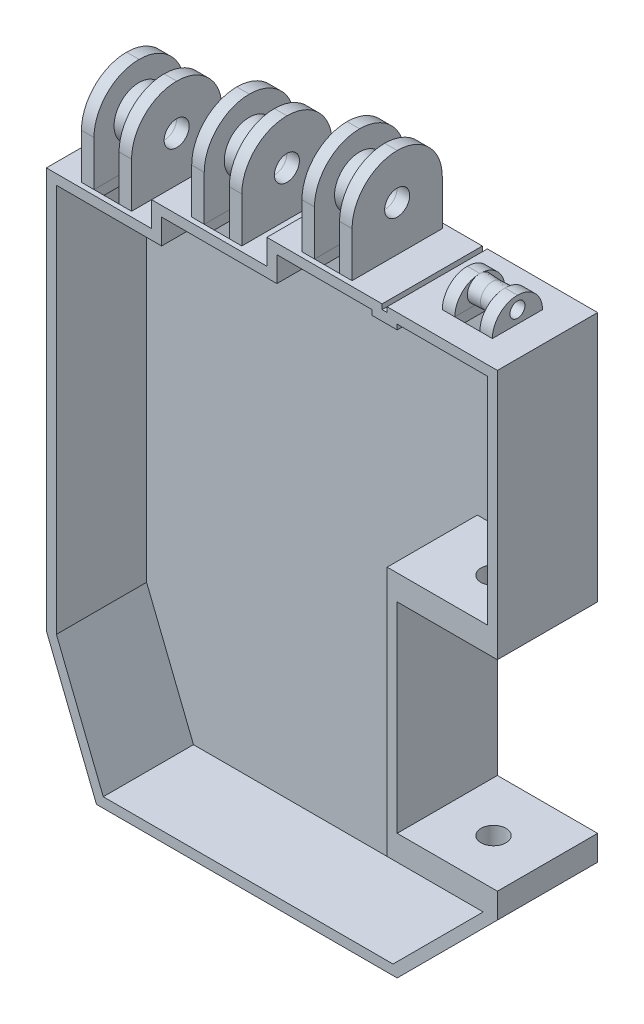
SolidWorks part; units mm, degrees
ref_plane "Front Plane" through (0, 0, 0) normal (0, 0, 1) x (1, 0, 0)
ref_plane "Top Plane" through (0, 0, 0) normal (0, 1, 0) x (1, 0, 0)
ref_plane "Right Plane" through (0, 0, 0) normal (1, 0, 0) x (0, 0, -1)
sketch "Sketch1" plane through (0, 0, 0) normal (0, 0, 1) x (1, 0, 0)
  line L0 (0, 0) -> (60, 0)
  line L1 (60, 0) -> (80, 20)
  line L2 (80, 20) -> (80, 115)
  line L3 (80, 115) -> (58, 115)
  line L4 (-10, 105) -> (11, 105)
  line L5 (-10, 105) -> (-10, 25)
  line L6 (-10, 25) -> (0, 0)
  line L7 (57, 115) -> (57, 114)
  line L8 (35, 115) -> (57, 115)
  line L9 (34, 115) -> (34, 110)
  line L10 (35, 115) -> (34, 115)
  line L11 (34, 110) -> (12, 110)
  line L12 (12, 110) -> (11, 110)
  line L13 (11, 110) -> (11, 105)
  line L14 (57, 115) -> (58, 115)
  line L15 (57, 114) -> (58, 114)
  line L16 (58, 114) -> (58, 115)
  dimension "D1" = 60
  dimension "D2" = 22
  dimension "D3" = 90
  dimension "D4" = 20
  dimension "D5" = 80
  dimension "D6" = 95
  dimension "D7" = 135
  dimension "D8" = 1
  dimension "D9" = 22
  dimension "D10" = 22
  dimension "D11" = 1
  dimension "D12" = 5
  dimension "D13" = 1
  dimension "D14" = 5
  dimension "D15" = 1
extrude "Boss-Extrude1" add sketch "Sketch1" along normal blind 20 contours L16 L15 L7 L8 L10 L9 L11 L12 L13 L4 L5 L6 L0 L1 L2 L3 region at (35.6394, 57.3872, 0)
sketch "Sketch2" plane through (0, 0, 20) normal (0, 0, 1) x (1, 0, 0)
  line L0 (80, 25) -> (60, 25)
  line L2 (60, 25) -> (60, 65)
  line L3 (60, 65) -> (80, 65)
  line L4 (80, 65) -> (80, 25)
  dimension "D1" = 20
  dimension "D2" = 5
  dimension "D3" = 40
extrude "Cut-Extrude1" cut sketch "Sketch2" against normal through all
shell "Shell1" thickness 2 removed face at (44.4444, 74.6111, 20)
sketch "Sketch3" plane through (0, 115, 0) normal (0, 1, 0) x (1, 0, 0)
  line L2 (74, -5) -> (64, -5)
  line L3 (74, -5) -> (74, -15)
  line L4 (74, -15) -> (64, -15)
  line L5 (64, -5) -> (64, -15)
  line L6 (74, -5) -> (64, -15) construction
  line L7 (74, -15) -> (64, -5) construction
  line L8 (66.5, -5) -> (66.5, -15)
  line L9 (71.5, -5) -> (71.5, -15)
  point P0 (69, -10)
  dimension "D1" = 10
  dimension "D2" = 10
  dimension "D3" = 5
  dimension "D4" = 2.5
extrude "Boss-Extrude2" add sketch "Sketch3" along normal blind 5 separate body contours L8 L2 L5 L4 | L2 L9 L4 L3 region at (72.75, 115, 10) region at (65.25, 115, 10)
fillet "Fillet2" radius 5 2 edges at (65.25, 120, 5) (65.25, 120, 15)
fillet "Fillet3" radius 5 2 edges at (72.75, 120, 5) (72.75, 120, 15)
sketch "Sketch5" plane through (66.5, 0, 0) normal (1, 0, 0) x (0, 0, -1)
  line L0 (-5, 115) -> (-15, 115) construction
  line L1 (-14.5, 115) -> (-5.5, 115)
  arc A0 (-5.5, 115) -> (-14.5, 115) centre (-10, 115) ccw
  point P5 (-10, 115)
  dimension "D1" = 9
extrude "Boss-Extrude3" [suppressed] add sketch "Sketch5" along normal blind 2.5 draft 10
mirror "Mirror1" [suppressed]
sketch "Sketch6" plane through (74, 0, 0) normal (1, 0, 0) x (0, 0, -1)
  circle A0 centre (-10, 117.5) radius 1.5
  point P3 (0, 0)
  dimension "D1" = 3
  dimension "D2" = 2.5
extrude "Cut-Extrude3" cut sketch "Sketch6" against normal up to surface (10 mm away) up to face at (64, 117.357, 10)
sketch "Sketch7" plane through (0, 115, 0) normal (0, 1, 0) x (1, 0, 0)
  line L0 (50, -1) -> (40, -1)
  line L1 (50, -1) -> (50, -19)
  line L2 (50, -19) -> (40, -19)
  line L3 (40, -1) -> (40, -19)
  line L4 (50, -1) -> (40, -19) construction
  line L5 (50, -19) -> (40, -1) construction
  line L6 (42.5, -1) -> (42.5, -19)
  line L7 (47.5, -1) -> (47.5, -19)
  line L8 (34, 0) -> (57, 0) construction
  line L10 (34, -20) -> (34, 0) construction
  point P0 (45, -10)
  point P13 (34, -10)
  dimension "D1" = 10
  dimension "D2" = 18
  dimension "D3" = 5
  dimension "D4" = 2.5
  dimension "D5" = 1
  dimension "D6" = 11
extrude "Boss-Extrude4" add sketch "Sketch7" along normal blind 18 separate body contours L6 L0 L3 L2 | L0 L7 L2 L1 region at (48.75, 115, 10) region at (41.25, 115, 10)
fillet "Fillet4" radius 9 2 edges at (41.25, 133, 1) (41.25, 133, 19)
fillet "Fillet5" radius 9 2 edges at (48.75, 133, 19) (48.75, 133, 1)
sketch "Sketch8" plane through (42.5, 0, 0) normal (1, 0, 0) x (0, 0, -1)
  circle A0 centre (-10, 124) radius 5
  dimension "D1" = 10
extrude "Boss-Extrude5" add sketch "Sketch8" along normal blind 2.5 draft 10
mirror "Mirror2" about plane through (45, 124, 10) normal (1, 0, 0) of "Boss-Extrude5"
sketch "Sketch9" plane through (50, 0, 0) normal (1, 0, 0) x (0, 0, -1)
  circle A0 centre (-10, 124) radius 2.5
  dimension "D1" = 5
extrude "Cut-Extrude4" cut sketch "Sketch9" against normal up to surface (10 mm away) up to face at (40, 122.9456, 10)
sketch "Sketch10" plane through (0, 110, 0) normal (0, 1, 0) x (1, 0, 0)
  line L0 (28, -1) -> (18, -1)
  line L1 (28, -1) -> (28, -19)
  line L2 (28, -19) -> (18, -19)
  line L3 (18, -1) -> (18, -19)
  line L4 (28, -1) -> (18, -19) construction
  line L5 (28, -19) -> (18, -1) construction
  line L6 (20.5, -1) -> (20.5, -19)
  line L7 (25.5, -1) -> (25.5, -19)
  line L8 (34, 0) -> (11, 0) construction
  line L10 (34, -20) -> (34, 0) construction
  point P0 (23, -10)
  point P11 (22.5, 0)
  dimension "D1" = 10
  dimension "D2" = 18
  dimension "D3" = 5
  dimension "D4" = 2.5
  dimension "D5" = 10
  dimension "D6" = 11
extrude "Boss-Extrude6" add sketch "Sketch10" along normal blind 18 separate body contours L6 L0 L3 L2 | L0 L7 L2 L1 region at (26.75, 110, 10) region at (19.25, 110, 10)
fillet "Fillet6" radius 9 2 edges at (19.25, 128, 19) (19.25, 128, 1)
fillet "Fillet7" radius 9 2 edges at (26.75, 128, 19) (26.75, 128, 1)
sketch "Sketch11" plane through (20.5, 0, 0) normal (1, 0, 0) x (0, 0, -1)
  circle A0 centre (-10, 119) radius 5
  dimension "D1" = 10
extrude "Boss-Extrude7" add sketch "Sketch11" along normal blind 2.5 draft 10
mirror "Mirror3" about plane through (23, 119, 10) normal (1, 0, 0) of "Boss-Extrude7"
sketch "Sketch12" plane through (28, 0, 0) normal (1, 0, 0) x (0, 0, -1)
  circle A0 centre (-10, 119) radius 2.5
  dimension "D1" = 5
extrude "Cut-Extrude5" cut sketch "Sketch12" against normal up to surface (10 mm away) up to face at (18, 117.9456, 10)
sketch "Sketch13" plane through (0, 105, 0) normal (0, 1, 0) x (1, 0, 0)
  line L0 (6, -1) -> (-4, -1)
  line L1 (6, -1) -> (6, -19)
  line L2 (6, -19) -> (-4, -19)
  line L3 (-4, -1) -> (-4, -19)
  line L4 (6, -1) -> (-4, -19) construction
  line L5 (6, -19) -> (-4, -1) construction
  line L6 (-1.5, -1) -> (-1.5, -19)
  line L7 (3.5, -1) -> (3.5, -19)
  line L8 (-10, 0) -> (11, 0) construction
  line L9 (-10, -20) -> (-10, 0) construction
  point P0 (1, -10)
  dimension "D1" = 10
  dimension "D2" = 18
  dimension "D3" = 5
  dimension "D4" = 2.5
  dimension "D5" = 10
  dimension "D6" = 11
extrude "Boss-Extrude8" add sketch "Sketch13" along normal blind 18 separate body contours L6 L0 L3 L2 | L0 L7 L2 L1 region at (4.75, 105, 10) region at (-2.75, 105, 10)
fillet "Fillet8" radius 9 2 edges at (-2.75, 123, 19) (-2.75, 123, 1)
fillet "Fillet9" radius 9 2 edges at (4.75, 123, 1) (4.75, 123, 19)
sketch "Sketch14" plane through (-1.5, 0, 0) normal (1, 0, 0) x (0, 0, -1)
  circle A0 centre (-10, 114) radius 5
  dimension "D1" = 10
extrude "Boss-Extrude9" add sketch "Sketch14" along normal blind 2.5 draft 10
mirror "Mirror4" about plane through (1, 114, 10) normal (1, 0, 0) of "Boss-Extrude9"
sketch "Sketch15" plane through (6, 0, 0) normal (1, 0, 0) x (0, 0, -1)
  circle A0 centre (-10, 114) radius 2.5
  dimension "D1" = 5
extrude "Cut-Extrude6" cut sketch "Sketch15" against normal up to surface (10 mm away) up to face at (-4, 112.9456, 10)
sketch "Sketch16" plane through (0, 115, 0) normal (0, 1, 0) x (1, 0, 0)
  line L0 (66.5, -15) -> (71.5, -15)
  line L1 (71.5, -5) -> (66.5, -5)
  line L2 (66.5, -5) -> (66.5, -19.1461)
  line L3 (42.5, -19) -> (47.5, -19)
  line L4 (47.5, -19) -> (47.5, -1)
  line L5 (47.5, -1) -> (42.5, -1)
  line L6 (42.5, -1) -> (42.5, -19)
  line L7 (71.5, -5) -> (71.5, -15)
  point P13 (0, 0)
  point P18 (0, 0)
  point P19 (0, 0)
  point P20 (0, 0)
extrude "Cut-Extrude7" cut sketch "Sketch16" against normal up to surface (2 mm away) contours L7 L1 L2 L0 | L5 L6 L3 L4 region at (69, 115, 10) region at (45, 115, 10) up to face at (45.5, 113, 11)
sketch "Sketch17" plane through (0, 110, 0) normal (0, 1, 0) x (1, 0, 0)
  line L0 (20.5, -19) -> (25.5, -19)
  line L1 (25.5, -19) -> (25.5, -0.8687)
  line L2 (25.5, -0.8687) -> (20.5, -1)
  line L3 (20.5, -1) -> (20.5, -19)
extrude "Cut-Extrude8" cut sketch "Sketch17" against normal up to surface (2 mm away) up to face at (24.5, 108, 11)
sketch "Sketch18" plane through (0, 105, 0) normal (0, 1, 0) x (1, 0, 0)
  line L0 (-1.5, -19) -> (3.5, -19)
  line L1 (3.5, -19) -> (3.5, -1)
  line L2 (3.5, -1) -> (-1.5, -1)
  line L3 (-1.5, -1) -> (-1.5, -19)
extrude "Cut-Extrude9" cut sketch "Sketch18" against normal up to surface (2 mm away) up to face at (2.5, 103, 11)
sketch "Sketch19" plane through (0, 70, 0) normal (0, 1, 0) x (1, 0, 0)
  line L0 (58, -2) -> (58, -20) construction
  line L1 (78, -2) -> (58, -2) construction
  circle A0 centre (70, -10.775) radius 2.5
  point P4 (58, -11)
  point P7 (68, -2)
  dimension "D3" = 5
  dimension "D1" = 12
  dimension "D2" = 9
extrude "Cut-Extrude10" cut sketch "Sketch19" against normal up to surface (50 mm away) up to face at (67.5858, 20, 11)
sketch "Sketch21" plane through (66.5, 0, 0) normal (1, 0, 0) x (0, 0, -1)
  circle A0 centre (-10, 117.5) radius 1.5
  circle A1 centre (-10, 117.5) radius 2.5
  circle M1 centre (-10, 117.5) radius 1.5
  dimension "D1" = 5
extrude "Boss-Extrude10" add sketch "Sketch21" along normal blind 2.5 draft 3 contours A1 M1 region at (66.5, 117.5, 12.4293)
mirror "Mirror7" about plane through (69, 0, 0) normal (1, 0, 0) of "Boss-Extrude10"
